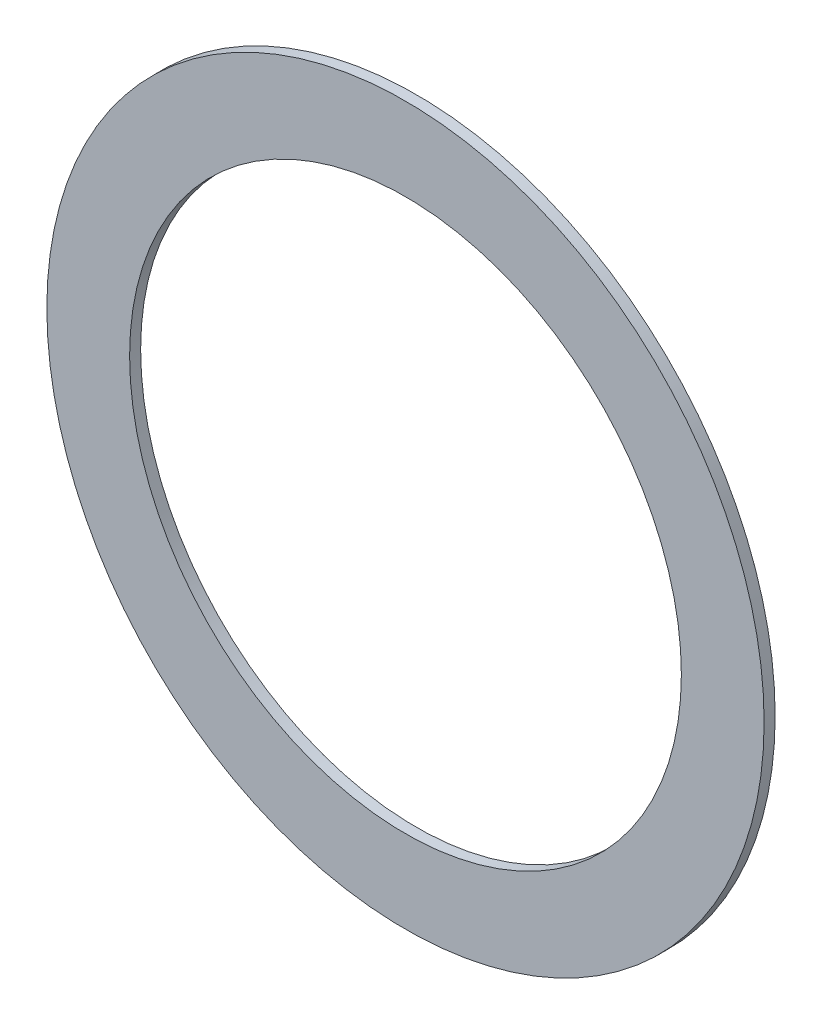
SolidWorks part; units mm, degrees
ref_plane "前基準面" through (0, 0, 0) normal (0, 0, 1) x (1, 0, 0)
ref_plane "上基準面" through (0, 0, 0) normal (0, 1, 0) x (1, 0, 0)
ref_plane "右基準面" through (0, 0, 0) normal (1, 0, 0) x (0, 0, -1)
sketch "草圖1" plane through (0, 0, 0) normal (0, 0, 1) x (1, 0, 0)
  circle A1 centre (0, 0) radius 65
extrude "填料-伸長1" add sketch "草圖1" along normal blind 2 contours A1
sketch "草圖2" plane through (0, 0, 2) normal (0, 0, 1) x (1, 0, 0)
  circle A0 centre (0, 0) radius 50
extrude "除料-伸長1" cut sketch "草圖2" against normal blind 2
sketch "草圖3" plane through (0, 0, 2) normal (0, 0, 1) x (1, 0, 0)
  line L0 (0, 0) -> (65, 0)
  line L1 (143.2456, 15) -> (143.2456, 20)
  line L2 (63.2456, 15) -> (143.2456, 15)
  line L3 (143.2456, 20) -> (61.8466, 20)
  line L4 (143.2456, -15) -> (63.2456, -15)
  circle A0 centre (0, 0) radius 65 construction
  point P8 (65, 0)
